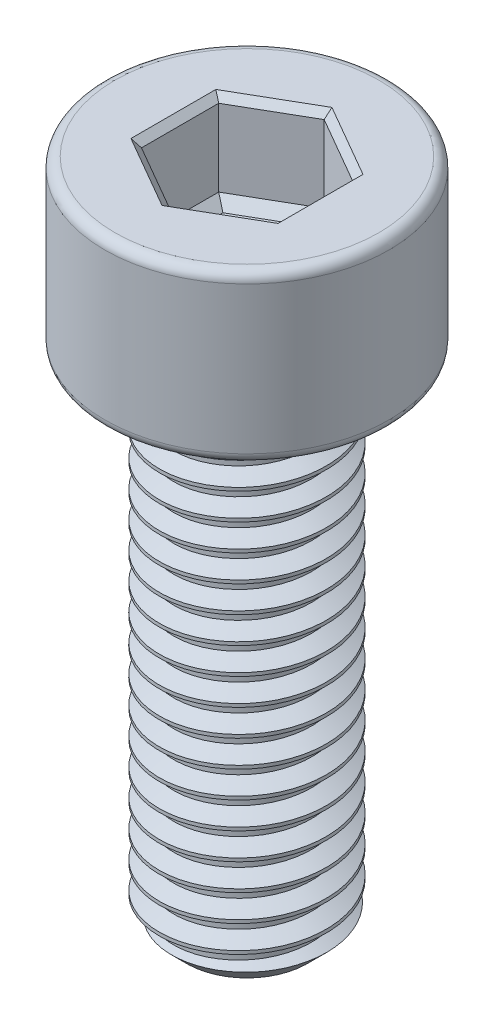
SolidWorks part; units mm, degrees
material "AISI Type A2 Tool Steel"
ref_plane "Front Plane" through (0, 0, 0) normal (0, 0, 1) x (1, 0, 0)
ref_plane "Top Plane" through (0, 0, 0) normal (0, 1, 0) x (1, 0, 0)
ref_plane "Right Plane" through (0, 0, 0) normal (1, 0, 0) x (0, 0, -1)
sketch "Sketch1" plane through (0, 0, 0) normal (0, 1, 0) x (1, 0, 0)
  circle A0 centre (0, 0) radius 2.5
  dimension "D1" = 5
extrude "Boss-Extrude1" add sketch "Sketch1" along normal blind 15
thread "Thread1" pitch 0.8 method cut profile "Thread Profile1" start angle 0, offset 1, length 0, pitch 0.8, diameter 5
ref_plane "Plane1" through (-2.5, 16, 0) normal (0, 0, 1) x (-1, 0, 0)
sketch "Thread Profile1" plane through (-2.5, 16, 0) normal (0, 0, 1) x (-1, 0, 0)
  line L0 (0, 0) -> (0, 0.8) construction
  line L11 (0, 0) -> (0, 0.7)
  line L12 (0, 0.7) -> (-0.433, 0.45)
  line L13 (-0.433, 0.45) -> (-0.433, 0.25)
  line L15 (-0.433, 0.25) -> (0, 0)
  line L17 (-0.433, 0.35) -> (0, 0.35) construction
  point P2 (0, 0)
  dimension "Pitch" = 0.8
  dimension "Profile_Angle" = 60
  dimension "Profile_Land" = 0.2
  dimension "Profile_Height" = 0.433
sketch "Sketch5" plane through (0, 15, 0) normal (0, 1, 0) x (1, 0, 0)
  circle A0 centre (0, 0) radius 4.25
  dimension "D1" = 8.5
extrude "Boss-Extrude2" add sketch "Sketch5" along normal blind 5
fillet "Fillet1" radius 0.3 2 edges at (0, 15, 4.25) (0, 20, 4.25)
sketch "Sketch6" plane through (0, 0, 0) normal (0, 0, 1) x (1, 0, 0)
  line L0 (0, 0) -> (0, 0.2882) construction
  line L1 (0, 0) -> (2.51, 0) construction
  line L2 (2.51, 0) -> (2.51, 0.7)
  line L3 (2.51, 0.7) -> (1.81, 0)
  line L4 (1.81, 0) -> (2.51, 0)
  dimension "D1" = 45
  dimension "D2" = 0.7
  dimension "D3" = 2.51
revolve "Cut-Revolve1" cut sketch "Sketch6" angle 360 about L0
sketch "Sketch7" plane through (0, 20, 0) normal (0, 1, 0) x (1, 0, 0)
  line L1 (0, 2.3094) -> (-2, 1.1547)
  line L2 (-2, 1.1547) -> (-2, -1.1547)
  line L3 (-2, -1.1547) -> (0, -2.3094)
  line L4 (0, -2.3094) -> (2, -1.1547)
  line L5 (2, -1.1547) -> (2, 1.1547)
  line L6 (2, 1.1547) -> (0, 2.3094)
  circle A0 centre (0, 0) radius 2 construction
  dimension "D1" = 4
extrude "Cut-Extrude1" cut sketch "Sketch7" against normal blind 2.5
chamfer "Chamfer1" distance 0.2 angle 45 6 edges at (-2, 20, 0) (-1, 20, 1.7321) (1, 20, 1.7321) (2, 20, 0) (1, 20, -1.7321) (-1, 20, -1.7321)
sketch "Sketch8" plane through (0, 17.5, 0) normal (0, 1, 0) x (1, 0, 0)
  line L1 (0, 2.3094) -> (-2, 1.1547)
  line L2 (-2, 1.1547) -> (-2, -1.1547)
  line L3 (-2, -1.1547) -> (0, -2.3094)
  line L4 (0, -2.3094) -> (2, -1.1547)
  line L5 (2, -1.1547) -> (2, 1.1547)
  line L6 (2, 1.1547) -> (0, 2.3094)
  circle A0 centre (0, 0) radius 2 construction
extrude "Cut-Extrude2" cut sketch "Sketch8" against normal blind 0.3 draft 45
